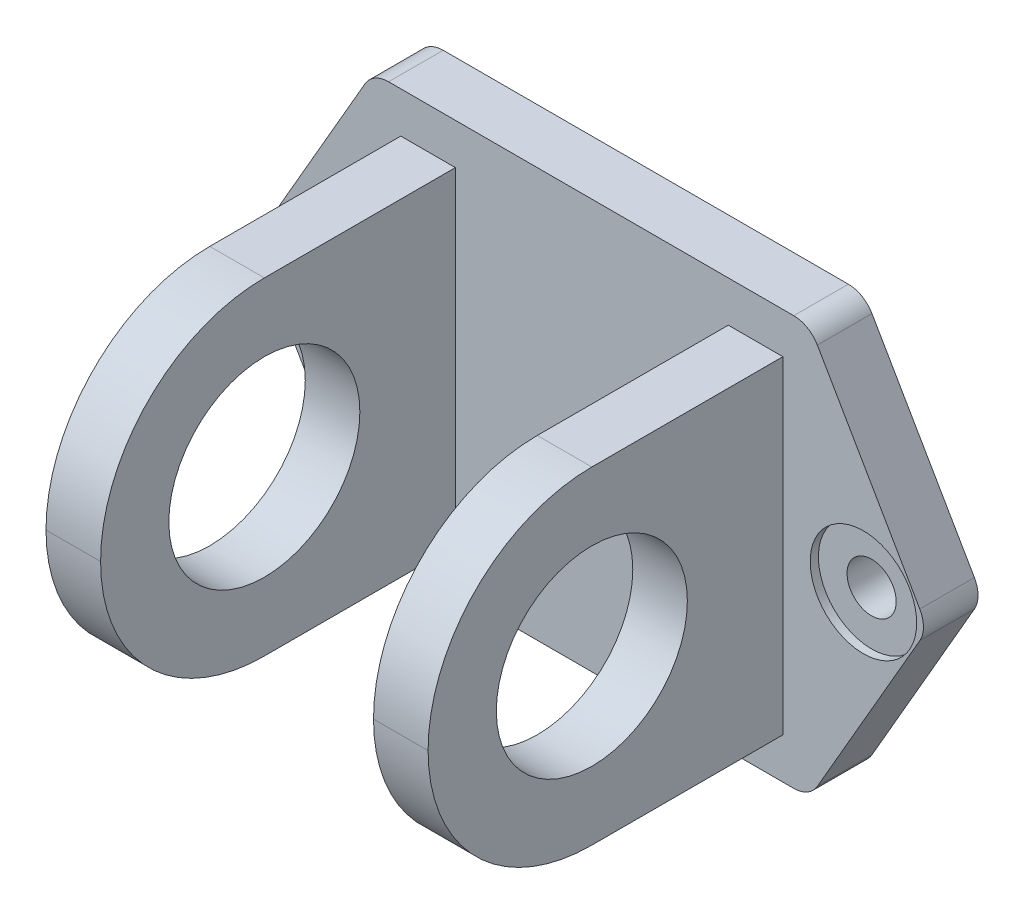
SolidWorks part; units mm, degrees
ref_plane "Plan de face" through (0, 0, 0) normal (0, 0, 1) x (1, 0, 0)
ref_plane "Plan de dessus" through (0, 0, 0) normal (0, 1, 0) x (1, 0, 0)
ref_plane "Plan de droite" through (0, 0, 0) normal (1, 0, 0) x (0, 0, -1)
sketch "Esquisse1" plane through (0, 0, 0) normal (0, 0, 1) x (1, 0, 0)
  line L0 (-254.7999, 65.8383) -> (-298.1012, -9.1617)
  line L1 (-254.7999, 65.8383) -> (-94.7999, 65.8383)
  line L3 (-254.7999, -84.1617) -> (-94.7999, -84.1617)
  line L5 (-298.1012, -9.1617) -> (-254.7999, -84.1617)
  line L6 (-94.7999, 65.8383) -> (-51.4987, -9.1617)
  line L7 (-51.4987, -9.1617) -> (-94.7999, -84.1617)
  line L8 (-174.7999, 83.9699) -> (-174.7999, 19.72) construction
  dimension "D1" = 150
  dimension "D2" = 120
  dimension "D3" = 75
  dimension "D4" = 160
  dimension "D5" = 160
  dimension "D6" = 120
  dimension "D7" = 75
  dimension "D8" = 80
  dimension "D9" = 80
  dimension "D10" = 80
extrude "Boss.-Extru.1" add sketch "Esquisse1" along normal blind 20
fillet "Congé1" radius 10 1 edges at (-94.7999, 65.8383, 10)
fillet "Congé2" radius 10 1 edges at (-254.7999, 65.8383, 10)
fillet "Congé3" radius 10 1 edges at (-298.1012, -9.1617, 10)
fillet "Congé4" radius 10 1 edges at (-254.7999, -84.1617, 10)
fillet "Congé5" radius 10 1 edges at (-94.7999, -84.1617, 10)
fillet "Congé7" radius 10 1 edges at (-51.4987, -9.1617, 10)
sketch "Esquisse2" plane through (0, 0, 20) normal (0, 0, 1) x (1, 0, 0)
  line L0 (-249.0264, -84.1617) -> (-100.5734, -84.1617) construction
  line L1 (-244.5542, 50.8383) -> (-224.5542, 50.8383)
  line L2 (-244.5542, 50.8383) -> (-244.5542, -69.1617)
  line L3 (-244.5542, -69.1617) -> (-224.5542, -69.1617)
  line L4 (-224.5542, 50.8383) -> (-224.5542, -69.1617)
  line L6 (-124.5542, 50.8383) -> (-104.5542, 50.8383)
  line L7 (-124.5542, 50.8383) -> (-124.5542, -69.1617)
  line L8 (-124.5542, -69.1617) -> (-104.5542, -69.1617)
  line L9 (-104.5542, 50.8383) -> (-104.5542, -69.1617)
  arc A0 (-295.2145, -4.1617) -> (-295.2145, -14.1617) centre (-286.5542, -9.1617) ccw construction
  point P13 (-296.5542, -9.1617)
  point P14 (-114.5542, -69.1617)
  point P15 (-114.5542, 50.8383)
  dimension "D1" = 120
  dimension "D2" = 20
  dimension "D3" = 15
  dimension "D4" = 20
  dimension "D5" = 100
  dimension "D6" = 52
  dimension "D7" = 15
  dimension "D8" = 0
extrude "Boss.-Extru.2" add sketch "Esquisse2" along normal blind 130
fillet "Congé8" radius 60 1 edges at (-114.5542, -69.1617, 150)
fillet "Congé9" radius 60 1 edges at (-114.5542, 50.8383, 150)
fillet "Congé10" radius 60 1 edges at (-234.5542, -69.1617, 150)
fillet "Congé11" radius 60 1 edges at (-234.5542, 50.8383, 150)
sketch "Esquisse3" plane through (-104.5542, 0, 0) normal (1, 0, 0) x (0, 0, -1)
  line L0 (-90, -69.1617) -> (-20, -69.1617) construction
  circle A0 centre (-90, -9.1617) radius 35
  dimension "D1" = 60
  dimension "D2" = 60
extrude "Enlèv. mat.-Extru.1" cut sketch "Esquisse3" against normal through all
sketch "Esquisse4" plane through (0, 0, 20) normal (0, 0, 1) x (1, 0, 0)
  line L0 (-100.5734, 65.8383) -> (-249.0264, 65.8383) construction
  circle A0 centre (-274.5542, -9.1617) radius 9
  arc A1 (-295.2145, -4.1617) -> (-295.2145, -14.1617) centre (-286.5542, -9.1617) ccw construction
  circle A2 centre (-75.0457, -9.1617) radius 9
  arc A3 (-54.3854, -14.1617) -> (-54.3854, -4.1617) centre (-63.0457, -9.1617) ccw construction
  point P7 (-296.5542, -9.1617)
  dimension "D1" = 75
  dimension "D3" = 12
  dimension "D2" = 22
extrude "Enlèv. mat.-Extru.2" cut sketch "Esquisse4" against normal through all
sketch "Esquisse5" plane through (0, 0, 20) normal (0, 0, 1) x (1, 0, 0)
  circle A0 centre (-274.5542, -9.1617) radius 19.3755
  circle A1 centre (-75.0457, -9.1617) radius 19.5009
extrude "Enlèv. mat.-Extru.3" cut sketch "Esquisse5" against normal blind 3
